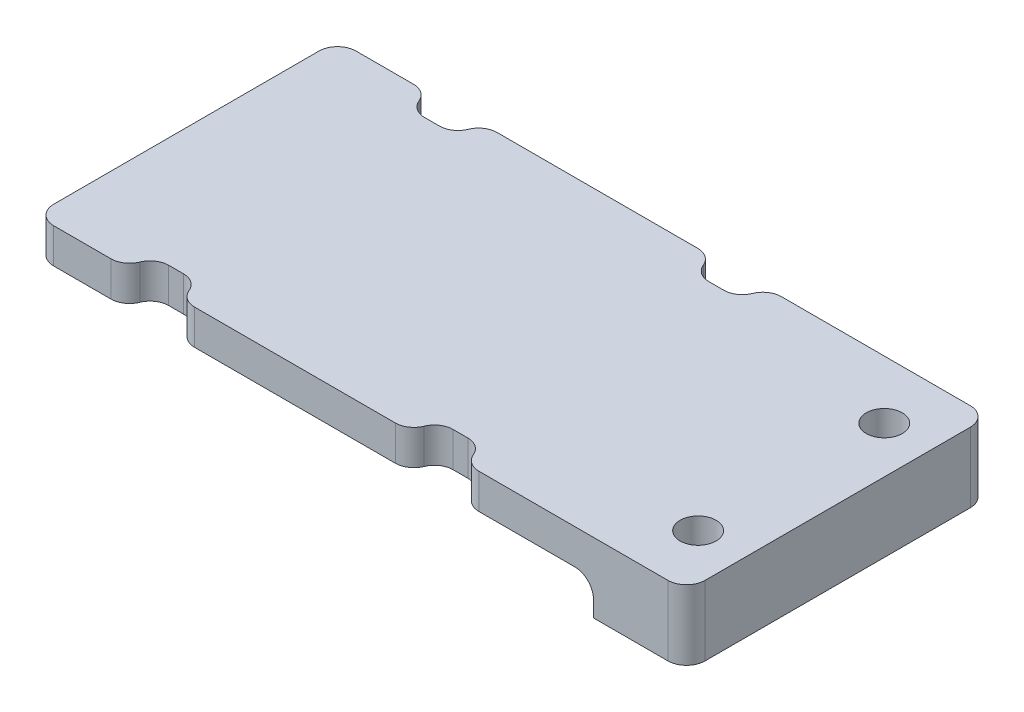
SolidWorks part; units mm, degrees
ref_plane "Front" through (0, 0, 0) normal (0, 0, 1) x (1, 0, 0)
ref_plane "Top" through (0, 0, 0) normal (0, 1, 0) x (1, 0, 0)
ref_plane "Right" through (0, 0, 0) normal (1, 0, 0) x (0, 0, -1)
sketch "Sketch1" plane through (0, 0, 0) normal (0, 1, 0) x (1, 0, 0)
  line L1 (-44.45, -20.6375) -> (44.45, -20.6375)
  line L2 (-44.45, -20.6375) -> (-44.45, 20.6375)
  line L3 (-44.45, 20.6375) -> (44.45, 20.6375)
  line L4 (44.45, -20.6375) -> (44.45, 20.6375)
  line L5 (-44.45, -20.6375) -> (44.45, 20.6375) construction
  line L6 (-44.45, 20.6375) -> (44.45, -20.6375) construction
  point P0 (0, 0)
  dimension "D1" = 88.9
  dimension "D2" = 41.275
extrude "Boss-Extrude1" add sketch "Sketch1" along normal blind 4.7625
sketch "Sketch3" plane through (0, 0, 0) normal (0, -1, 0) x (1, 0, 0)
  line L0 (44.45, -20.6375) -> (-44.45, -20.6375) construction
  line L1 (44.45, 20.6375) -> (31.75, 20.6375)
  line L2 (44.45, 20.6375) -> (44.45, -20.6375)
  line L3 (44.45, -20.6375) -> (31.75, -20.6375)
  line L4 (31.75, 20.6375) -> (31.75, -20.6375)
  dimension "D1" = 12.7
extrude "Boss-Extrude2" add sketch "Sketch3" along normal blind 4.7625
sketch "Sketch8" plane through (0, 4.7625, 0) normal (0, 1, 0) x (1, 0, 0)
  line L4 (44.45, -20.6375) -> (44.45, 20.6375) construction
  line L5 (-50, 0) -> (50, 0) construction
  point P0 (38.1, 12.7)
  point P4 (38.1, -12.7)
  dimension "D1" = 25.4
  dimension "D2" = 12.7
  dimension "D3" = 6.35
hole_wizard "#10 (0.1935) Diameter Hole1" positions "Sketch8" profile "Sketch7" hole size "#10" standard "ANSI Inch" end condition through all
sketch "Sketch7" plane through (38.1, 4.7625, -12.7) normal (1, 0, 0) x (0, 0, 1)
  line L0 (0, 0) -> (0, 9.525)
  line L1 (0, 9.525) -> (2.4574, 9.525)
  line L2 (2.4574, 9.525) -> (2.4574, 0)
  line L5 (2.4574, 0) -> (0, 0)
  line L11 (0, -6.35) -> (0, 107.95) construction
  dimension "Thru Hole Dia." = 4.9149
  dimension "Thru Hole Depth" = 9.525
sketch "Sketch9" plane through (0, 4.7625, 0) normal (0, 1, 0) x (1, 0, 0)
  line L14 (44.45, 20.6375) -> (-44.45, 20.6375) construction
  line L20 (7.248, 20.6375) -> (13.598, 20.6375)
  line L21 (7.248, 20.6375) -> (7.248, 17.4625)
  line L22 (7.248, 17.4625) -> (13.598, 17.4625)
  line L23 (13.598, 20.6375) -> (13.598, 17.4625)
  line L24 (-44.45, -20.6375) -> (44.45, -20.6375) construction
  line L25 (-31.5516, 20.6375) -> (-25.2016, 20.6375)
  line L26 (-31.5516, 20.6375) -> (-31.5516, 17.4625)
  line L27 (-31.5516, 17.4625) -> (-25.2016, 17.4625)
  line L28 (-25.2016, 20.6375) -> (-25.2016, 17.4625)
  line L29 (-31.5516, -20.6375) -> (-25.2016, -20.6375)
  line L30 (-31.5516, -20.6375) -> (-31.5516, -17.4625)
  line L31 (-31.5516, -17.4625) -> (-25.2016, -17.4625)
  line L32 (-25.2016, -20.6375) -> (-25.2016, -17.4625)
  line L34 (7.248, -20.6375) -> (13.598, -20.6375)
  line L35 (7.248, -20.6375) -> (7.248, -17.4625)
  line L36 (7.248, -17.4625) -> (13.598, -17.4625)
  line L37 (13.598, -20.6375) -> (13.598, -17.4625)
  line L38 (44.45, -20.6375) -> (44.45, 20.6375) construction
  dimension "D1" = 3.175
  dimension "D2" = 6.35
  dimension "D3" = 32.4495
  dimension "D4" = 76.0016
extrude "Cut-Extrude1" cut sketch "Sketch9" against normal through all
fillet "Fillet1" radius 2.54 12 edges at (-25.2016, 2.3812, 20.6375) (-31.5516, 2.3812, 20.6375) (-44.45, 2.3813, 20.6375) (-31.5516, 2.3812, -20.6375) (-25.2016, 2.3812, -20.6375) (7.248, 2.3812, -20.6375) (13.598, 2.3812, -20.6375) (44.45, 0, -20.6375) (44.45, 0, 20.6375) (13.598, 2.3812, 20.6375) (7.248, 2.3812, 20.6375) (-44.45, 2.3813, -20.6375)
fillet "Fillet2" radius 2.54 9 edges at (-31.5516, 2.3812, -17.4625) (-25.2016, 2.3813, -17.4625) (13.598, 2.3813, -17.4625) (7.248, 2.3812, -17.4625) (31.75, 0, 0) (13.598, 2.3813, 17.4625) (7.248, 2.3812, 17.4625) (-31.5516, 2.3812, 17.4625) (-25.2016, 2.3813, 17.4625)
